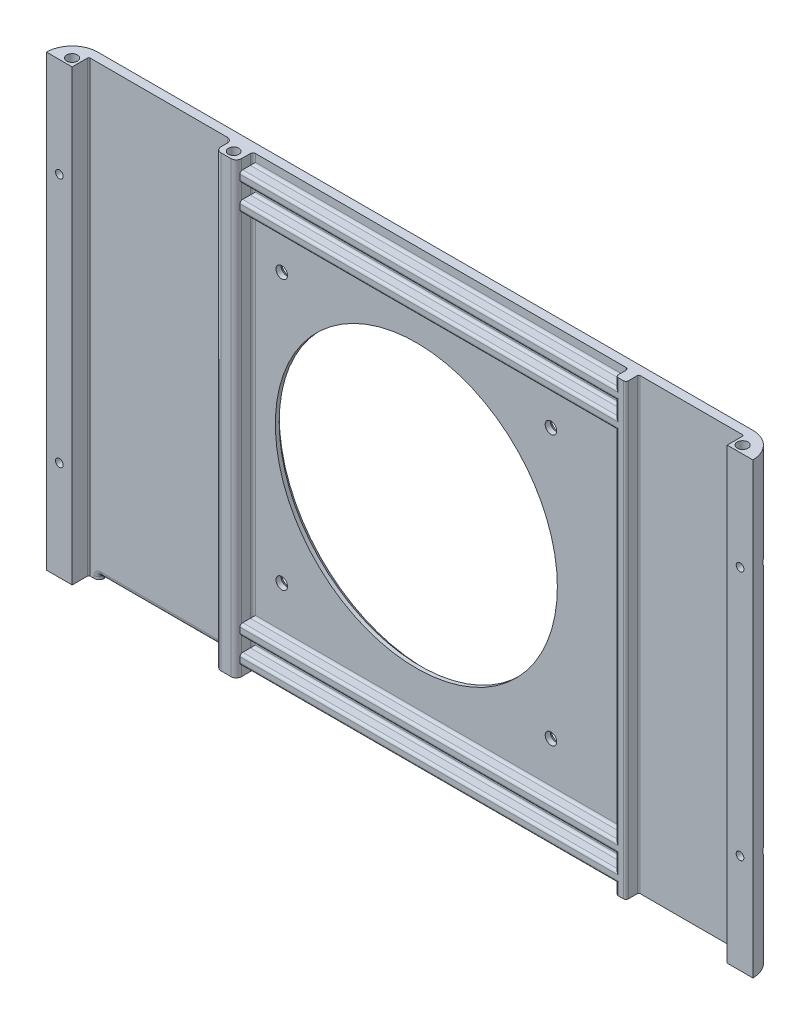
SolidWorks part; units mm, degrees
ref_plane "前视基准面" through (0, 0, 0) normal (0, 0, 1) x (1, 0, 0)
ref_plane "上视基准面" through (0, 0, 0) normal (0, 1, 0) x (1, 0, 0)
ref_plane "右视基准面" through (0, 0, 0) normal (1, 0, 0) x (0, 0, -1)
other "Configuration Table"
sketch "草图2" plane through (0, 0, 0) normal (0, 1, 0) x (1, 0, 0)
  line L0 (-127.75, -5) -> (-127.75, 1.5)
  line L1 (-137.75, -5) -> (137.75, -5)
  line L2 (-137.75, -5) -> (-137.75, 5)
  line L3 (-137.75, 5) -> (137.75, 5)
  line L4 (137.75, -5) -> (137.75, 5)
  line L5 (-137.75, -5) -> (137.75, 5) construction
  line L6 (-137.75, 5) -> (137.75, -5) construction
  line L7 (-127.75, 1.5) -> (127.75, 1.5)
  line L8 (127.75, 1.5) -> (127.75, -5)
  point P0 (0, 0)
  dimension "D1" = 275.5
  dimension "D2" = 10
  dimension "D3" = 6.5
  dimension "D4" = 10
  dimension "D5" = 10
extrude "凸台-拉伸1" add sketch "草图2" along normal blind 175 contours L7 L8 L1 L4 L3 L2 L0 region at (0, 0, -2.656)
fillet "圆角1" radius 10 2 edges at (-137.75, 87.5, -5) (137.75, 87.5, -5)
fillet "圆角2" radius 0.5 2 edges at (-127.75, 87.5, -1.5) (127.75, 87.5, -1.5)
sketch "草图3" plane through (0, 0, 0) normal (0, -1, 0) x (1, 0, 0)
  line L0 (-77.24, -5) -> (-77.24, -1.5)
  line L1 (-127.75, -5) -> (127.75, -5) construction
  line L2 (-127.25, -1.5) -> (127.25, -1.5) construction
  line L3 (-123.65, -5) -> (-123.65, -1.5)
  line L4 (-77.24, -1.5) -> (-123.65, -1.5)
  line L5 (-77.24, -5) -> (-123.65, -5)
  dimension "D1" = 214.99
  dimension "D2" = 46.41
extrude "切除-拉伸1" cut sketch "草图3" against normal blind 1.5
fillet "圆角3" radius 0.5 2 edges at (-77.24, 1.5, -3.25) (-123.65, 1.5, -3.25)
fillet "圆角4" radius 2 10 edges at (-77.24, 0.5, -1.5) (-77.3864, 1.3536, -1.5) (-123.5036, 1.3536, -1.5) (-123.65, 0.5, -1.5) (-100.445, 1.5, -1.5) (-123.65, 0.5, -5) (-123.5036, 1.3536, -5) (-100.445, 1.5, -5) (-77.3864, 1.3536, -5) (-77.24, 0.5, -5)
sketch "草图6" plane through (0, 0, -1.5) normal (0, 0, 1) x (1, 0, 0)
  line L0 (-127.25, 175) -> (127.25, 0) construction
  line L2 (127.25, 175) -> (-127.25, 0) construction
  line L3 (-52.5, 35) -> (52.5, 35) construction
  line L4 (-52.5, 35) -> (-52.5, 140) construction
  line L5 (-52.5, 140) -> (52.5, 140) construction
  line L6 (52.5, 35) -> (52.5, 140) construction
  line L7 (-52.5, 35) -> (52.5, 140) construction
  line L8 (-52.5, 140) -> (52.5, 35) construction
  circle A0 centre (-52.5, 140) radius 2.25
  circle A1 centre (52.5, 140) radius 2.25
  circle A2 centre (52.5, 35) radius 2.25
  circle A3 centre (-52.5, 35) radius 2.25
  circle A4 centre (0, 87.5) radius 55
  point P5 (0, 87.5)
  dimension "D1" = 4.5
  dimension "D2" = 4.5
  dimension "D3" = 4.5
  dimension "D4" = 4.5
extrude "切除-拉伸4" cut sketch "草图6" against normal blind 6
sketch "草图8" plane through (0, 0, 5) normal (0, 0, 1) x (1, 0, 0)
  line L0 (-127.75, 175) -> (-137.75, 0) construction
  line L1 (-127.75, 0) -> (-137.75, 175) construction
  line L2 (0, 0) -> (0, 175) construction
  line L3 (-127.25, 175) -> (127.25, 175) construction
  line L5 (137.75, 175) -> (137.75, 0) construction
  circle A0 centre (-132.75, 136.25) radius 1.5
  circle A1 centre (-132.75, 38.75) radius 1.5
  circle A2 centre (132.75, 38.75) radius 1.5
  circle A3 centre (132.75, 136.25) radius 1.5
  point P13 (-132.75, 87.5)
  dimension "D3" = 5
  dimension "D1" = 97.5
  dimension "D2" = 48.75
extrude "切除-拉伸5" cut sketch "草图8" against normal blind 56
sketch "草图10" plane through (0, 0, -5) normal (0, 0, -1) x (-1, 0, 0)
  circle A0 centre (132.75, 38.75) radius 1.5 construction
  circle A1 centre (132.75, 136.25) radius 1.5 construction
  circle A2 centre (-132.75, 38.75) radius 1.5 construction
  circle A3 centre (-132.75, 136.25) radius 1.5 construction
  circle A4 centre (132.75, 38.75) radius 1.5
  circle A5 centre (132.75, 136.25) radius 1.5
  circle A6 centre (-132.75, 38.75) radius 1.5
  circle A7 centre (-132.75, 136.25) radius 1.5
  circle A12 centre (132.75, 38.75) radius 3
  circle A13 centre (132.75, 136.25) radius 3
  circle A14 centre (-132.75, 38.75) radius 3
  circle A15 centre (-132.75, 136.25) radius 3
  dimension "D1" = 1.5
extrude "切除-拉伸6" cut sketch "草图10" against normal blind 7
sketch "草图12" plane through (0, 0, -1.5) normal (0, 0, 1) x (1, 0, 0)
  line L0 (-67.75, 175) -> (-67.75, 0) construction
  line L1 (-127.25, 175) -> (127.25, 175) construction
  line L2 (-75.24, 0) -> (127.25, 0) construction
  line L4 (-63.75, 175) -> (-63.75, 0)
  line L5 (-71.75, 175) -> (-71.75, 0)
  line L6 (-71.75, 175) -> (-63.75, 175)
  line L7 (-71.75, 0) -> (-63.75, 0)
  line L8 (-137.75, 175) -> (-137.75, 0) construction
  dimension "D1" = 70
  dimension "D2" = 4
  dimension "D3" = 4
extrude "凸台-拉伸3" add sketch "草图12" along normal blind 6.5
sketch "草图11" plane through (0, 0, -1.5) normal (0, 0, 1) x (1, 0, 0)
  line L0 (82.75, 175) -> (82.75, 171)
  line L1 (-127.25, 175) -> (-71.75, 175) construction
  line L2 (-75.24, 0) -> (-71.75, 0) construction
  line L3 (86.75, 175) -> (86.75, 0)
  line L4 (82.75, 0) -> (86.75, 0)
  line L5 (82.75, 175) -> (86.75, 175)
  line L6 (137.75, 175) -> (137.75, 0) construction
  line L7 (-67.75, 0) -> (-67.75, 175) construction
  line L8 (-137.75, 175) -> (-137.75, 0) construction
  line L9 (82.75, 171) -> (-67.75, 171)
  line L10 (-63.75, 167) -> (82.75, 167)
  line L11 (-63.75, 8) -> (82.75, 8)
  line L12 (-67.75, 4) -> (82.75, 4)
  line L13 (-67.75, 171) -> (-67.75, 4)
  line L14 (-63.75, 8) -> (-63.75, 14)
  line L15 (-63.75, 157) -> (82.75, 157)
  line L16 (60, 27.5) -> (-60, 27.5) construction
  line L17 (60, 27.5) -> (60, 147.5) construction
  line L18 (60, 147.5) -> (-60, 147.5) construction
  line L19 (-60, 27.5) -> (-60, 147.5) construction
  line L20 (60, 27.5) -> (-60, 147.5) construction
  line L21 (60, 147.5) -> (-60, 27.5) construction
  line L22 (82.75, 161) -> (-63.75, 161)
  line L23 (-63.75, 14) -> (82.75, 14)
  line L24 (-63.75, 18) -> (82.75, 18)
  line L25 (-63.75, 18) -> (-63.75, 157)
  line L26 (82.75, 14) -> (82.75, 8)
  line L27 (82.75, 4) -> (82.75, 0)
  line L28 (-63.75, 161) -> (-63.75, 167)
  line L29 (82.75, 157) -> (82.75, 18)
  line L30 (82.75, 167) -> (82.75, 161)
  circle A0 centre (0, 87.5) radius 55 construction
  circle A1 centre (0, 87.5) radius 55 construction
  dimension "D1" = 51
  dimension "D2" = 4
  dimension "D3" = 70
  dimension "D4" = 4
  dimension "D5" = 4
  dimension "D6" = 4
  dimension "D7" = 4
  dimension "D8" = 4
  dimension "D9" = 2
  dimension "D10" = 2
extrude "凸台-拉伸2" add sketch "草图11" along normal blind 5
fillet "圆角6" radius 0.5 1 edges at (86.75, 87.5, -1.5)
fillet "圆角7" radius 2 3 edges at (-63.75, 87.5, 5) (-71.75, 87.5, 5) (-71.75, 87.5, -1.5)
fillet "圆角11" radius 1 32 edges at (9.5, 157, -1.5) (9.4682, 157, 3.5) (9.4682, 161, 3.5) (9.5, 161, -1.5) (9.4682, 167, 3.5) (9.5, 167, -1.5) (9.4682, 171, 3.5) (9.5, 171, -1.5) (9.5, 8, -1.5) (9.5, 18, -1.5) (9.4682, 18, 3.5) (9.4682, 14, 3.5) (9.5, 14, -1.5) (9.5, 4, -1.5) (9.4682, 8, 3.5) (9.4682, 4, 3.5) (82.75, 87.5, 3.5) (86.75, 87.5, 3.5) (82.75, 164, 3.5) (82.75, 173, 3.5) (82.75, 2, 3.5) (82.75, 11, 3.5) (82.75, 164, -1.5) (82.75, 173, -1.5) (82.75, 2, -1.5) (82.75, 11, -1.5) (82.75, 87.5, -1.5) (-63.75, 173, -1.5) (-63.75, 164, -1.5) (-63.75, 87.5, -1.5) (-63.75, 11, -1.5) (-63.75, 2, -1.5)
sketch "草图4" plane through (0, 0, 0) normal (0, -1, 0) x (1, 0, 0)
  line L0 (-75.24, -5) -> (127.75, -5) construction
  circle A0 centre (-130.75, 2) radius 2.1
  circle A1 centre (130.75, 2) radius 2.1
  circle A2 centre (-67.75, 2) radius 2.05
  dimension "D3" = 4.2
  dimension "D4" = 4.2
  dimension "D7" = 70
  dimension "D1" = 7
  dimension "D2" = 7
  dimension "D5" = 7
  dimension "D6" = 7
extrude "切除-拉伸2" cut sketch "草图4" against normal blind 6
sketch "草图5" plane through (0, 175, 0) normal (0, 1, 0) x (1, 0, 0)
  circle A0 centre (130.75, -2) radius 2.1 construction
  circle A1 centre (-130.75, -2) radius 2.1 construction
  circle A2 centre (130.75, -2) radius 2.1
  circle A3 centre (-130.75, -2) radius 2.1
  circle A4 centre (-67.75, -2) radius 2.05 construction
  circle A5 centre (-67.75, -2) radius 2.05
extrude "切除-拉伸3" cut sketch "草图5" against normal blind 6
chamfer "倒角1" distance 2 angle 45 1 edges at (-55, 87.5, -5)
sketch "草图13" plane through (0, 0, -5) normal (0, 0, -1) x (-1, 0, 0)
  circle A0 centre (-52.5, 35) radius 2.25 construction
  circle A1 centre (52.5, 35) radius 2.25 construction
  circle A2 centre (52.5, 140) radius 2.25 construction
  circle A3 centre (-52.5, 140) radius 2.25 construction
  circle A4 centre (-52.5, 35) radius 2.25
  circle A5 centre (52.5, 35) radius 2.25
  circle A6 centre (52.5, 140) radius 2.25
  circle A7 centre (-52.5, 140) radius 2.25
  circle A8 centre (-52.5, 35) radius 3.25
  circle A9 centre (52.5, 35) radius 3.25
  circle A10 centre (52.5, 140) radius 3.25
  circle A11 centre (-52.5, 140) radius 3.25
  dimension "D1" = 1
extrude "切除-拉伸7" cut sketch "草图13" against normal blind 1.5
fillet "圆角12" radius 0.5 8 edges at (49.25, 35, -5) (49.25, 35, -3.5) (-55.75, 35, -5) (-55.75, 35, -3.5) (-55.75, 140, -5) (-55.75, 140, -3.5) (49.25, 140, -5) (49.25, 140, -3.5)
